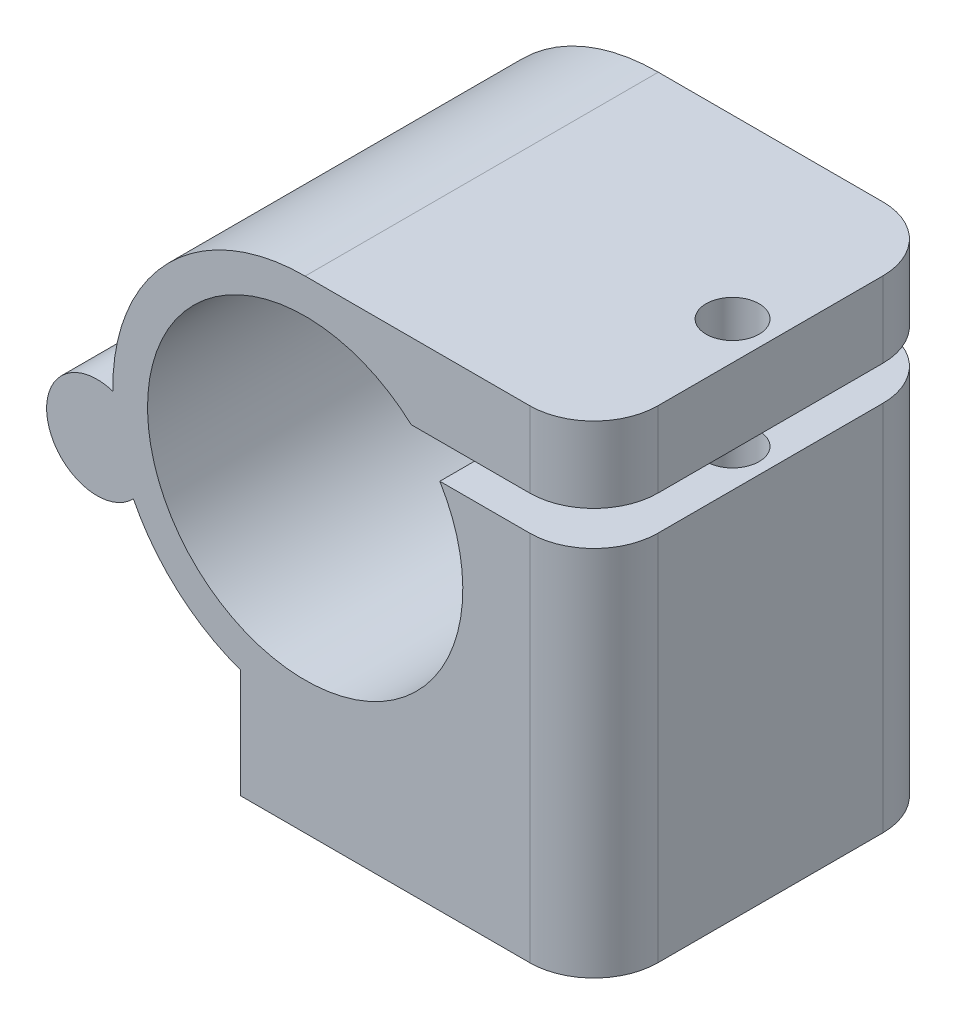
SolidWorks part; units mm, degrees
material "6063-T5"
ref_plane "Front Plane" through (0, 0, 0) normal (0, 0, 1) x (1, 0, 0)
ref_plane "Top Plane" through (0, 0, 0) normal (0, 1, 0) x (1, 0, 0)
ref_plane "Right Plane" through (0, 0, 0) normal (1, 0, 0) x (0, 0, -1)
sketch "Sketch1" plane through (0, 0, 0) normal (0, 1, 0) x (1, 0, 0)
  line L0 (-14, -14) -> (-14, 14)
  line L1 (-14, -14) -> (14, -14)
  line L2 (-14, 14) -> (14, 14)
  line L3 (14, -14) -> (14, 14)
  line L4 (-14, -14) -> (14, 14) construction
  line L5 (-14, 14) -> (14, -14) construction
  line L6 (-14, 8.92) -> (-8.92, 8.92)
  line L7 (-8.92, 8.92) -> (8.92, 8.92)
  line L8 (-8.92, 8.92) -> (-8.92, -8.92)
  line L9 (-8.92, -8.92) -> (8.92, -8.92)
  line L10 (8.92, -8.92) -> (8.92, 8.92)
  line L11 (0, -8.92) -> (0, 8.92)
  circle A0 centre (-14, 14) radius 5.08
  circle A1 centre (-8.92, 8.92) radius 1.524
  circle A11 centre (8.92, 8.92) radius 1.524
  circle A12 centre (8.92, -8.92) radius 1.524
  circle A13 centre (-8.92, -8.92) radius 1.524
  circle A14 centre (0, 8.92) radius 2.54
  circle A15 centre (0, -8.92) radius 2.54
  circle A16 centre (0, 0) radius 2.54
  circle A17 centre (-8.92, 0) radius 1.0795
  circle A18 centre (8.92, 0) radius 4.7625
  point P1 (0, 0)
  point P21 (0, 0)
  dimension "D3" = 10.16
  dimension "D5" = 3.048
  dimension "D7" = 17.84
  dimension "D8" = 5.08
  dimension "D9" = 5.08
  dimension "D10" = 5.08
  dimension "D11" = 2.159
  dimension "D12" = 9.525
  dimension "D1" = 28
  dimension "D2" = 28
  dimension "D4" = 5.08
  dimension "D6" = 4
extrude "Boss-Extrude1" add sketch "Sketch1" along normal blind 10.5 contours L0 A0 L2 | A18 L10 A12 L9 A15 A13 L8 A17 A1 L0 L1 L3 L2 A0 L7 A14 A11 | A17 L8 A13 L9 A15 L11 A16 A14 L7 A1 | A18 L10 A11 L7 A14 L11 A16 A15 L9 A12 | L10 A11 L7 | L10 A18 | L10 A18 | A12 | A15 | A16 | A14 | A1 | A17 | A13 | A11 region at (-13.604, 0, 2.54) region at (-11.844, 0, -11.844) region at (-4.8147, 0, 0) region at (4.1362, 0, 0) region at (9.1356, 0, -9.1356) region at (10.9413, 0, 0) region at (6.8987, 0, 0)
sketch "Sketch2" plane through (0, 0, -14) normal (0, 0, -1) x (-1, 0, 0)
  line L0 (0, 0) -> (8.89, 0)
  line L3 (14, 0) -> (-14, 0) construction
  line L4 (8.89, 0) -> (8.89, 10.5)
  line L5 (14, 10.5) -> (-14, 10.5) construction
  line L6 (8.89, 10.5) -> (8.89, 35.5)
  line L7 (8.89, 35.5) -> (8.89, 38.25)
  line L8 (24.14, 23) -> (-6.36, 23)
  circle A2 centre (8.89, 23) radius 12.5
  circle A3 centre (8.89, 23) radius 15.25
  line M12 (14, 0) -> (14, 10.5)
  line M13 (14, 10.5) -> (-14, 10.5)
  dimension "D1" = 8.89
  dimension "D2" = 25
  dimension "D3" = 2.75
extrude "Boss-Extrude3" add sketch "Sketch2" against normal up to surface (28 mm away) contours A3 L8 A2 M12 M13 | L4 A3 M12 M13 | L8 A3 A2 M13 | A3 L4 M13 | L8 A3 L7 A2 | L7 A3 L8 A2 region at (-5.5708, 9.391, -14) region at (-11.2933, 9.2563, -14) region at (2.0475, 15.9155, -14) region at (-19.4658, 15.4333, -14) region at (-17.752, 31.862, -14) region at (-0.028, 31.862, -14) up to face at (0, 5.25, 14)
sketch "Sketch3" plane through (0, 0, 14) normal (0, 0, 1) x (1, 0, 0)
  line L0 (-21.3897, 22.914) -> (-21.3897, 18.914)
  line L1 (-21.3897, 18.914) -> (-25.3897, 18.914)
  circle A0 centre (-8.89, 23) radius 12.5 construction
  circle A1 centre (-25.3897, 18.914) radius 4
  dimension "D1" = 4
  dimension "D2" = 4
extrude "Boss-Extrude4" add sketch "Sketch3" against normal up to surface (28 mm away) contours A1 up to face at (-0.8013, 11.6358, -14)
sketch "Sketch5" plane through (0, 0, 14) normal (0, 0, 1) x (1, 0, 0)
  line L0 (-8.89, 10.5) -> (14, 10.5)
  line L1 (14, 10.5) -> (14, 29.5)
  line L2 (14, 29.5) -> (4.9054, 29.5)
  circle A0 centre (-8.89, 23) radius 12.5 construction
  arc A1 (-0.1543, 10.5) -> (-24.1373, 22.7129) centre (-8.89, 23) ccw construction
  arc A2 (-0.1543, 10.5) -> (4.9054, 29.5) centre (-8.89, 23) ccw
  arc M2 (-0.1543, 10.5) -> (-24.1373, 22.7129) centre (-8.89, 23) ccw
  line M8 (14, 10.5) -> (-0.1543, 10.5)
  dimension "D1" = 19
extrude "Boss-Extrude5" add sketch "Sketch5" against normal up to surface (28 mm away) contours L1 L2 M2 M8 region at (9.3049, 19.2225, 14) up to face at (-6.1855, 12.3103, -14)
sketch "Sketch6" plane through (0, 0, 14) normal (0, 0, 1) x (1, 0, 0)
  line L0 (14, 29.5) -> (14, 32.25)
  line L1 (14, 32.25) -> (-0.4824, 32.25)
  line L2 (14, 29.5) -> (1.7871, 29.5)
  circle A0 centre (-8.89, 23) radius 12.5 construction
  arc A1 (1.7871, 29.5) -> (-0.4824, 32.25) centre (-8.89, 23) ccw
  dimension "D1" = 2.75
extrude "Cut-Extrude1" cut sketch "Sketch6" against normal through all
sketch "Sketch7" plane through (0, 0, 14) normal (0, 0, 1) x (1, 0, 0)
  line L0 (-8.89, 38.25) -> (14, 29.5)
  line L1 (14, 29.5) -> (14, 38.25)
  line L2 (14, 38.25) -> (-8.89, 38.25)
  line L3 (-0.4824, 32.25) -> (14, 32.25)
  arc A0 (3.2344, 32.25) -> (-24.1373, 22.7129) centre (-8.89, 23) ccw construction
  arc A1 (3.2344, 32.25) -> (-8.89, 38.25) centre (-8.89, 23) ccw
  arc M4 (3.2344, 32.25) -> (-24.1373, 22.7129) centre (-8.89, 23) ccw
extrude "Boss-Extrude6" add sketch "Sketch7" against normal up to surface (28 mm away) contours L0 L3 L1 L2 M4 | L3 L0 M4 region at (6.6347, 35.691, 14) region at (3.8278, 32.9406, 14) up to face at (-7.9356, 18.0863, -14)
sketch "Sketch8" plane through (0, 38.25, 0) normal (0, 1, 0) x (1, 0, 0)
  line L0 (14, 0) -> (11, 0)
  line L1 (14, 14) -> (14, -14) construction
  circle A0 centre (11, 0) radius 2.1
  dimension "D2" = 4.2
  dimension "D1" = 3
extrude "Cut-Extrude2" cut sketch "Sketch8" against normal blind 12.75 contours A0 region at (8.9594, 38.25, 0)
extrude "Cut-Extrude3" cut sketch "Sketch1<4>" along normal blind 5.2 contours A13 | A17 | A1 | A11 | A12
sketch "Sketch1<4>" plane through (0, 0, 0) normal (0, 1, 0) x (1, 0, 0) same geometry as "Sketch1"
extrude "Cut-Extrude4" cut sketch "Sketch1<5>" along normal blind 9.5 contours A15 | A16 | A14
sketch "Sketch1<5>" plane through (0, 0, 0) normal (0, 1, 0) x (1, 0, 0) same geometry as "Sketch1"
extrude "Cut-Extrude5" cut sketch "Sketch1<6>" along normal blind 14.5 contours A18
sketch "Sketch1<6>" plane through (0, 0, 0) normal (0, 1, 0) x (1, 0, 0) same geometry as "Sketch1"
fillet "Fillet1" radius 5.08 1 edges at (14, 14.75, 14) type face fillet first side face at (-5.0317, 21.1416, 14) second side face at (14, 14.75, 0)
fillet "Fillet2" radius 5.08 1 edges at (14, 35.25, 14) type face fillet first side face at (-5.9554, 21.1416, 14) second side face at (14, 35.25, 0)
fillet "Fillet3" radius 5.08 1 edges at (14, 35.25, -14) type face fillet first side face at (14, 35.25, -2.54) second side face at (-5.0317, 21.1416, -14)
fillet "Fillet4" radius 5.08 1 edges at (14, 14.75, -14) type face fillet first side face at (14, 14.75, -2.54) second side face at (-5.9554, 21.1416, -14)
